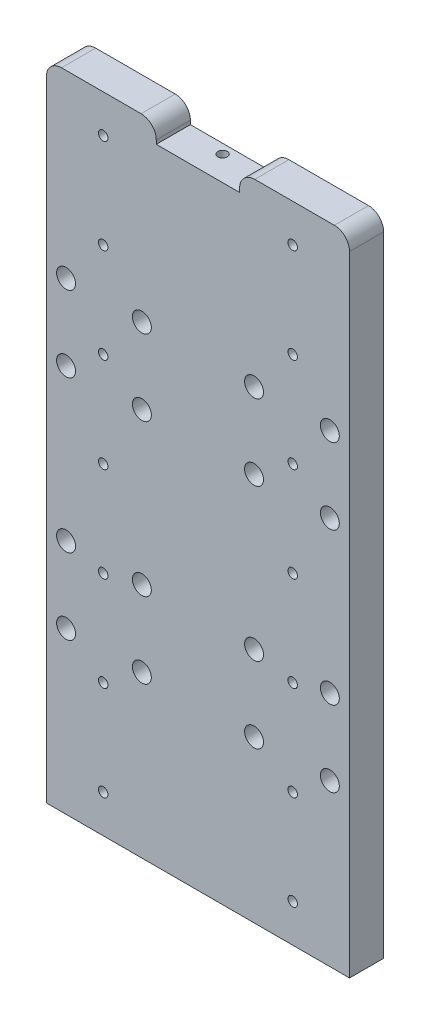
SolidWorks part; units mm, degrees
ref_plane "Front" through (0, 0, 0) normal (0, 0, 1) x (1, 0, 0)
ref_plane "Top" through (0, 0, 0) normal (0, 1, 0) x (1, 0, 0)
ref_plane "Right" through (0, 0, 0) normal (1, 0, 0) x (0, 0, -1)
sketch "Esquisse1" plane through (0, 0, 0) normal (0, 0, 1) x (1, 0, 0)
  line L1 (0, 0) -> (80, 0)
  line L2 (0, 0) -> (0, 170)
  line L3 (0, 170) -> (80, 170)
  line L4 (80, 0) -> (80, 170)
  dimension "D1" = 80
  dimension "D2" = 170
extrude "Boss.-Extru.1" add sketch "Esquisse1" along normal blind 9
sketch "Esquisse2" plane through (0, 0, 9) normal (0, 0, 1) x (1, 0, 0)
  line L0 (40, 0) -> (40, 170) construction
  line L1 (0, 0) -> (80, 0) construction
  line L2 (80, 170) -> (0, 170) construction
  line L3 (15, 10) -> (15, 35) construction
  circle A0 centre (15, 10) radius 1.25
  circle A1 centre (65, 10) radius 1.25
  circle A2 centre (15, 35) radius 1.25
  circle A3 centre (65, 35) radius 1.25
  circle A4 centre (15, 60) radius 1.25
  circle A5 centre (65, 60) radius 1.25
  circle A6 centre (15, 85) radius 1.25
  circle A7 centre (65, 85) radius 1.25
  circle A8 centre (15, 110) radius 1.25
  circle A9 centre (65, 110) radius 1.25
  circle A10 centre (15, 135) radius 1.25
  circle A11 centre (65, 135) radius 1.25
  circle A12 centre (15, 160) radius 1.25
  circle A13 centre (65, 160) radius 1.25
  circle A14 centre (15, 185) radius 1.25
  circle A15 centre (65, 185) radius 1.25
  dimension "D2" = 2.5
  dimension "D1" = 50
  dimension "D3" = 10
  dimension "D5" = 25
  dimension "D4" = 8
extrude "Enlèv. mat.-Extru.1" cut sketch "Esquisse2" against normal through all
sketch "Esquisse4" plane through (0, 0, 9) normal (0, 0, 1) x (1, 0, 0)
  line L0 (40, 170) -> (40, 165) construction
  line L1 (80, 170) -> (0, 170) construction
  line L2 (51, 165) -> (29, 165)
  line L3 (29, 165) -> (29, 170)
  line L4 (29, 170) -> (51, 170)
  line L5 (51, 165) -> (51, 170)
  dimension "D1" = 22
  dimension "D2" = 5
extrude "Enlèv. mat.-Extru.3" cut sketch "Esquisse4" against normal through all
sketch "Esquisse5" plane through (0, 165, 0) normal (0, 1, 0) x (1, 0, 0)
  line L0 (40, 0) -> (40, -2.5) construction
  line L3 (29, 0) -> (51, 0) construction
  circle A0 centre (40, -2.5) radius 1.25
  dimension "D1" = 2.5
  dimension "D2" = 2.5
extrude "Enlèv. mat.-Extru.4" cut sketch "Esquisse5" against normal blind 10
sketch "Esquisse6" plane through (0, 0, 9) normal (0, 0, 1) x (1, 0, 0)
  line L0 (74.8, 122.5) -> (74.8, 82.5) construction
  line L1 (40, 165) -> (40, 0) construction
  line L2 (29, 165) -> (51, 165) construction
  line L3 (0, 0) -> (80, 0) construction
  line L5 (74.8, 82.5) -> (40, 82.5) construction
  line L6 (5.2, 122.5) -> (5.2, 82.5) construction
  line L7 (74.8, 122.5) -> (64.8, 122.5) construction
  line L8 (64.8, 122.5) -> (64.8, 124.5729) construction
  circle A0 centre (74.8, 122.5) radius 2.5
  circle A1 centre (74.8, 62.5) radius 2.5
  circle A2 centre (74.8, 102.5) radius 2.5
  circle A3 centre (74.8, 42.5) radius 2.5
  circle A4 centre (5.2, 42.5) radius 2.5
  circle A5 centre (5.2, 102.5) radius 2.5
  circle A6 centre (5.2, 62.5) radius 2.5
  circle A7 centre (5.2, 122.5) radius 2.5
  circle A8 centre (54.8, 102.5) radius 2.5
  circle A9 centre (54.8, 122.5) radius 2.5
  circle A10 centre (54.8, 42.5) radius 2.5
  circle A11 centre (54.8, 62.5) radius 2.5
  circle A12 centre (25.2, 62.5) radius 2.5
  circle A13 centre (25.2, 42.5) radius 2.5
  circle A14 centre (25.2, 122.5) radius 2.5
  circle A15 centre (25.2, 102.5) radius 2.5
  dimension "D3" = 5
  dimension "D5" = 20
  dimension "D1" = 34.8
  dimension "D2" = 20
  dimension "D4" = 20
extrude "Enlèv. mat.-Extru.5" cut sketch "Esquisse6" against normal through all
fillet "Congé1" radius 4 4 edges at (80, 170, 4.5) (0, 170, 4.5) (51, 170, 4.5) (29, 170, 4.5)
